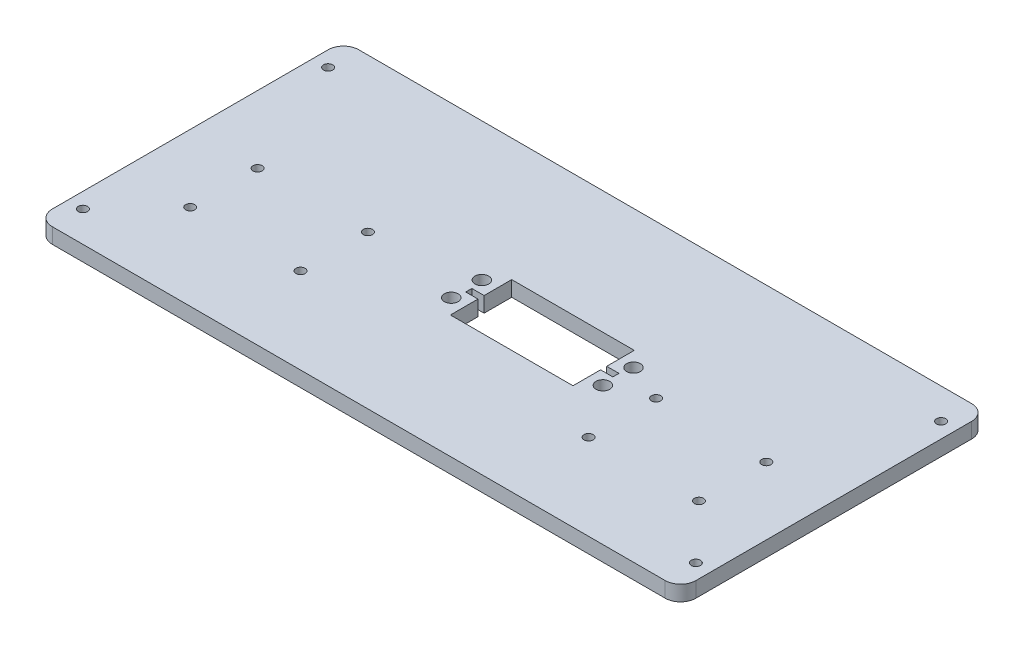
SolidWorks part; units mm, degrees
ref_plane "前视基准面" through (0, 0, 0) normal (0, 0, 1) x (1, 0, 0)
ref_plane "上视基准面" through (0, 0, 0) normal (0, 1, 0) x (1, 0, 0)
ref_plane "右视基准面" through (0, 0, 0) normal (1, 0, 0) x (0, 0, -1)
other "Configuration Table"
sketch "草图1" plane through (0, 0, 0) normal (0, 1, 0) x (1, 0, 0)
  line L1 (-210, 100) -> (0, 100)
  line L2 (-210, 100) -> (-210, 0)
  line L3 (-210, 0) -> (0, 0)
  line L4 (0, 100) -> (0, 0)
  dimension "D1" = 210
  dimension "D2" = 100
extrude "凸台-拉伸1" add sketch "草图1" along normal blind 5
fillet "圆角1" radius 5 4 edges at (0, 2.5, -100) (-210, 2.5, -100) (-210, 2.5, 0) (0, 2.5, 0)
sketch "草图2" plane through (0, 5, 0) normal (0, 1, 0) x (1, 0, 0)
  line L0 (-5, 100) -> (-205, 100) construction
  line L1 (-210, 95) -> (-210, 5) construction
  line L2 (-105, 100) -> (-105, 0) construction
  line L3 (-205, 0) -> (-5, 0) construction
  line L4 (-210, 50) -> (0, 50) construction
  line L5 (0, 5) -> (0, 95) construction
  circle A0 centre (-205, 90) radius 1.5
  circle A1 centre (-205, 10) radius 1.5
  circle A2 centre (-5, 10) radius 1.5
  circle A3 centre (-5, 90) radius 1.5
  dimension "D1" = 3
  dimension "D2" = 10
  dimension "D3" = 5
extrude "切除-拉伸1" cut sketch "草图2" against normal up to surface (5 mm away) up to face at (-105, 0, -50)
sketch "草图4" plane through (0, 0, 0) normal (0, -1, 0) x (1, 0, 0)
  line L0 (-5, -100) -> (-205, -100) construction
  line L1 (-115.1, -60) -> (-75.1, -60)
  line L2 (-115.1, -60) -> (-115.1, -51)
  line L3 (-115.1, -40) -> (-75.1, -40)
  line L4 (-75.1, -60) -> (-75.1, -51)
  line L5 (-210, -95) -> (-210, -5) construction
  line L6 (-205, 0) -> (-5, 0) construction
  line L7 (0, -5) -> (0, -95) construction
  line L8 (-119.1, -50) -> (-71.1, -50) construction
  line L9 (-95.1, -40) -> (-95.1, -60) construction
  line L10 (-115.1, -49) -> (-119.1, -49)
  line L11 (-115.1, -51) -> (-119.1, -51)
  line L12 (-119.1, -49) -> (-119.1, -51)
  line L13 (-75.1, -51) -> (-71.1, -51)
  line L14 (-71.1, -49) -> (-71.1, -51)
  line L15 (-75.1, -49) -> (-71.1, -49)
  line L16 (-115.1, -49) -> (-115.1, -40)
  line L17 (-75.1, -49) -> (-75.1, -40)
  circle A0 centre (-119.85, -45) radius 2.25
  circle A1 centre (-119.85, -55) radius 2.25
  circle A2 centre (-70.35, -55) radius 2.25
  circle A3 centre (-70.35, -45) radius 2.25
  dimension "D6" = 4.5
  dimension "D1" = 40
  dimension "D2" = 94.9
  dimension "D3" = 40
  dimension "D4" = 75.1
  dimension "D5" = 49.5
  dimension "D7" = 10
  dimension "D8" = 2
  dimension "D9" = 4
  dimension "D10" = 10
extrude "切除-拉伸2" cut sketch "草图4" against normal up to surface (5 mm away) up to face at (-5, 5, -91.5)
sketch "草图6" plane through (0, 0, 0) normal (0, -1, 0) x (1, 0, 0)
  line L0 (-210, -95) -> (-210, -5) construction
  line L1 (-5, -100) -> (-205, -100) construction
  line L3 (-105, 0) -> (-105, -100) construction
  line L4 (-205, 0) -> (-5, 0) construction
  circle A4 centre (-188, -50) radius 1.5
  circle A5 centre (-188, -28) radius 1.5
  circle A6 centre (-152, -50) radius 1.5
  circle A7 centre (-152, -28) radius 1.5
  circle A8 centre (-58, -50) radius 1.5
  circle A9 centre (-22, -50) radius 1.5
  circle A10 centre (-58, -28) radius 1.5
  circle A11 centre (-22, -28) radius 1.5
  point P2 (-152, -50)
  point P3 (0, 0)
  point P4 (-152.028, -29.4208)
  point P7 (0, 0)
  point P8 (-152, -28)
  dimension "D2" = 50
  dimension "D3" = 22
  dimension "D6" = 3
  dimension "D7" = 3
  dimension "D8" = 22
  dimension "D9" = 50
  dimension "D10" = 36
extrude "切除-拉伸3" cut sketch "草图6" against normal up to surface (5 mm away) up to face at (-70.35, 5, -42.75)
